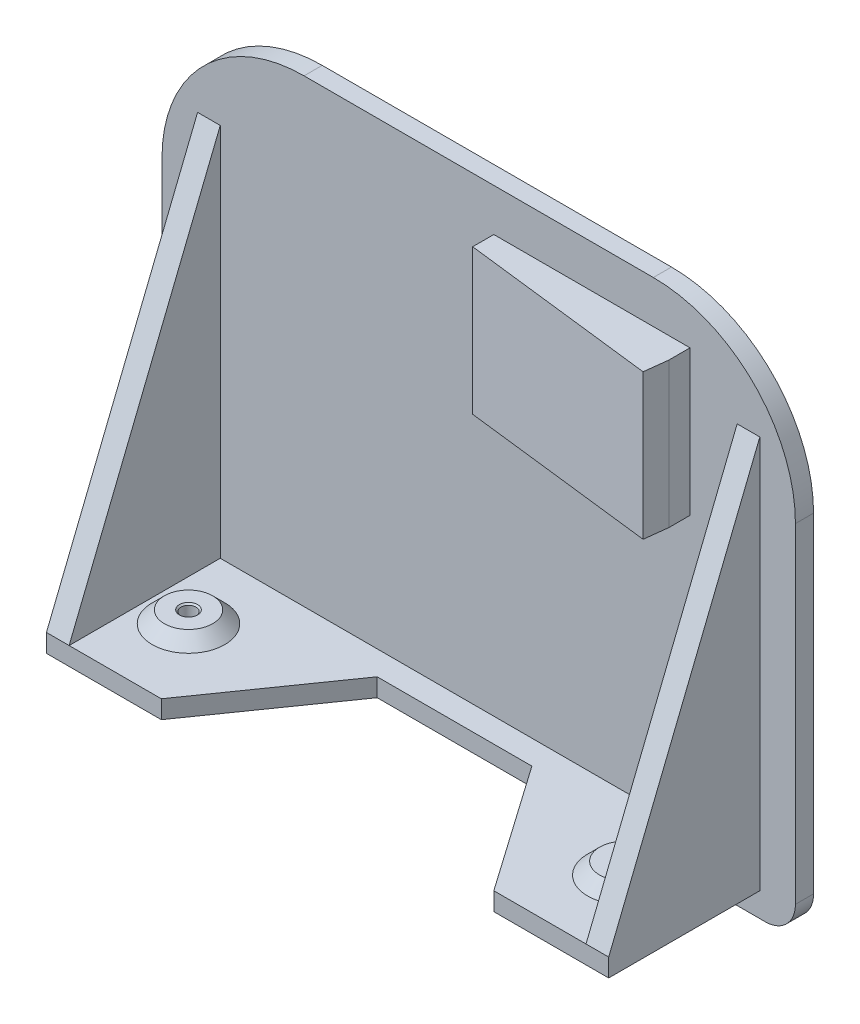
SolidWorks part; units mm, degrees
ref_plane "Front Plane" through (0, 0, 0) normal (0, 0, 1) x (1, 0, 0)
ref_plane "Top Plane" through (0, 0, 0) normal (0, 1, 0) x (1, 0, 0)
ref_plane "Right Plane" through (0, 0, 0) normal (1, 0, 0) x (0, 0, -1)
sketch "Sketch1" plane through (0, 0, 0) normal (0, 0, 1) x (1, 0, 0)
  line L0 (-52.3875, 0) -> (52.3875, 0) construction
  line L1 (0, 46.0375) -> (0, -46.0375) construction
  line L2 (-28.8875, 46.0375) -> (28.8875, 46.0375)
  line L5 (-28.8875, -46.0375) -> (28.8875, -46.0375) construction
  line L6 (-47.3875, -37) -> (47.3875, -37)
  line L7 (-52.3875, 22.5375) -> (-52.3875, 0)
  line L8 (-52.3875, 0) -> (-52.3875, -32)
  line L9 (52.3875, 0) -> (52.3875, -32)
  line L10 (52.3875, 22.5375) -> (52.3875, 0)
  arc A0 (-28.8875, 46.0375) -> (-52.3875, 22.5375) centre (-28.8875, 22.5375) ccw
  arc A3 (-28.8875, -46.0375) -> (-52.3875, -22.5375) centre (-28.8875, -22.5375) cw construction
  arc A4 (28.8875, -46.0375) -> (52.3875, -22.5375) centre (28.8875, -22.5375) ccw construction
  arc A5 (28.8875, 46.0375) -> (52.3875, 22.5375) centre (28.8875, 22.5375) cw
  arc A6 (52.3875, -32) -> (47.3875, -37) centre (47.3875, -32) cw
  arc A7 (-52.3875, -32) -> (-47.3875, -37) centre (-47.3875, -32) ccw
  point P6 (0, 0)
  point P22 (-52.3875, 0)
  point P24 (0, -40)
  point P27 (52.3875, -37)
  point P30 (-52.3875, -37)
  dimension "D3" = 23.5
  dimension "D4" = 5
  dimension "D5" = 37
  dimension "D1" = 104.775
  dimension "D2" = 92.075
extrude "plate" add sketch "Sketch1" along normal blind 3
sketch "Sketch9" plane through (0, 0, 0) normal (1, 0, 0) x (0, 0, -1)
  line L0 (-3, 32) -> (-3, -33)
  line L1 (-3, -33) -> (-28, -33)
  line L2 (-28, -33) -> (-28, -30)
  line L3 (-28, -30) -> (-3, 32)
  line L4 (-3, 22.5375) -> (-3, -32) construction
  dimension "D1" = 3
  dimension "D2" = 65
  dimension "D3" = 25
  dimension "D4" = 33
extrude "bracket" add sketch "Sketch9" along normal mid plane 93
sketch "Sketch10" plane through (0, 0, 0) normal (1, 0, 0) x (0, 0, -1)
  line L0 (-28, -30) -> (-3, -30)
  line L2 (-3, -30) -> (-3, 32)
  line L3 (-3, 32) -> (-28, -30)
  line L4 (-3, -33) -> (-3, 32) construction
extrude "bracket hollow" cut sketch "Sketch10" against normal mid plane 85.5
sketch "construct mount holes" plane through (0, -30, -27) normal (0, 1, 0) x (1, 0, 0)
  line L0 (-42.75, -30) -> (42.75, -30) construction
  line L3 (0, -28.65) -> (0, -25.35) construction
  line L4 (-36, -42) -> (36, -42) construction
  point P0 (-36, -42)
  point P7 (0, -42)
  point P8 (36, -42)
  dimension "D1" = 12
  dimension "D2" = 36
sketch "Sketch29" plane through (0, -30, 0) normal (0, 1, 0) x (1, 0, 0)
  circle A0 centre (36, -15) radius 4
  circle A1 centre (-36, -15) radius 4
  dimension "D1" = 8
extrude "insert boss" add sketch "Sketch29" along normal blind 2
chamfer "insert chamfer" distance 2 angle 45 2 edges at (36, -30, 11) (-36, -30, 11)
hole_wizard "M3 mount holes" positions "Sketch11" profile "Sketch12" hole size "M3" standard "ISO" end condition through all
sketch "Sketch11" plane through (0, -33, 0) normal (0, -1, 0) x (-1, 0, 0)
  line L1 (0, 1.65) -> (0, -1.65) construction
  line L2 (-46.5, -3) -> (46.5, -3) construction
  point P0 (-36, -15)
  point P8 (36, -15)
  dimension "D1" = 12
  dimension "D2" = 36
sketch "Sketch12" plane through (36, -33, 15) normal (1, 0, 0) x (0, 0, -1)
  line L0 (0, 0) -> (0, 5)
  line L1 (0, 5) -> (1.5, 5)
  line L2 (1.25, 4.75) -> (1.25, 0.25)
  line L3 (1.25, 0.25) -> (1.5, 0)
  line L5 (1.5, 0) -> (0, 0)
  line L6 (-1.25, 0.25) -> (-1.5, 0) construction
  line L7 (1.5, 5) -> (1.25, 4.75)
  line L8 (-1.5, 5) -> (-1.25, 4.75) construction
  line L11 (0, -6.35) -> (0, 107.95) construction
  dimension "Thru Hole Dia." = 2.5
  dimension "Thru Hole Depth" = 5
  dimension "Near C'Sink Dia." = 3
  dimension "Near C'Sink Angle" = 90
  dimension "Far C'Sink Dia." = 3
  dimension "Far C'Sink Angle" = 90
sketch "Sketch30" plane through (0, -30, 0) normal (0, 1, 0) x (1, 0, 0)
  line L0 (-27.5, -28) -> (-12.7956, -7)
  line L1 (-42.75, -28) -> (42.75, -28) construction
  line L2 (-12.7956, -7) -> (12.7956, -7)
  line L3 (12.7956, -7) -> (27.5, -28)
  line L4 (27.5, -28) -> (-27.5, -28)
  line L5 (-42.75, -3) -> (42.75, -3) construction
  line L7 (0, -7) -> (0, -28) construction
  line L8 (0, -1.65) -> (0, 1.65) construction
  dimension "D1" = 4
  dimension "D2" = 55
  dimension "D3" = 55
extrude "Cut-Extrude1" cut sketch "Sketch30" against normal through all
sketch "Sketch5" plane through (0, 0, 0) normal (0, 1, 0) x (1, 0, 0)
  line L0 (2.5, -6.5) -> (34.5, -10.3158)
  line L1 (34.5, -10.3158) -> (34.955, -6.5)
  line L2 (34.955, -6.5) -> (2.5, -6.5) construction
  line L3 (0, 0) -> (0, -3) construction
  line L4 (28.8875, -3) -> (-28.8875, -3) construction
  line L6 (2.5, -6.5) -> (2.5, -3)
  line L7 (-42.75, -3) -> (42.75, -3) construction
  line L8 (2.5, -3) -> (34.955, -3)
  line L9 (34.955, -3) -> (34.955, -6.5)
  dimension "D3" = 6.8
  dimension "D1" = 32
  dimension "D2" = 2.5
  dimension "D4" = 3.5
extrude "top-cam-boss" add sketch "Sketch5" along normal blind 24 from offset 15
equation "\"top angle\"=6.8"
equation "\"bot angle\"=20.4"
equation "\"D3@Sketch5\"=\"top angle\""
equation "\"D1@Sketch13\"=\"bot angle\""
